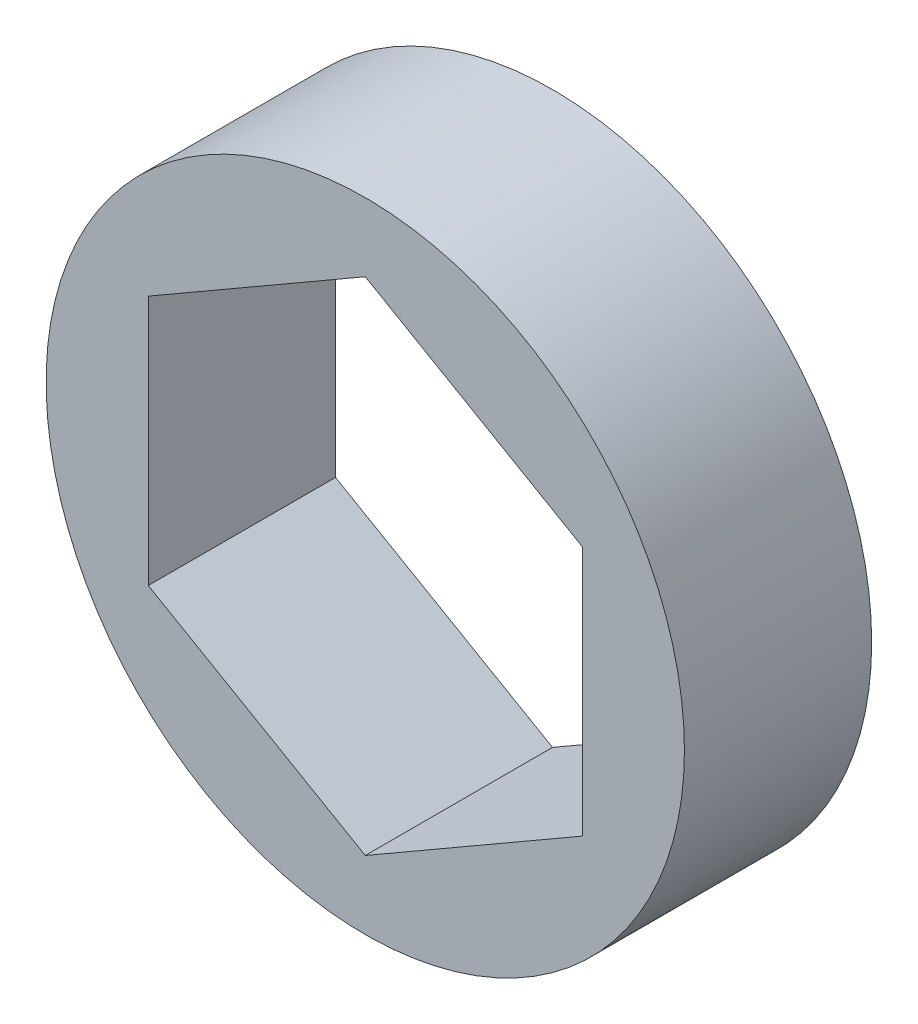
SolidWorks part; units mm, degrees
material "PET"
ref_plane "Front" through (0, 0, 0) normal (0, 0, 1) x (1, 0, 0)
ref_plane "Top" through (0, 0, 0) normal (0, 1, 0) x (1, 0, 0)
ref_plane "Right" through (0, 0, 0) normal (1, 0, 0) x (0, 0, -1)
sketch "Sketch1" plane through (0, 0, 0) normal (0, 0, 1) x (1, 0, 0)
  line L1 (0, 7.479) -> (-6.477, 3.7395)
  line L2 (-6.477, 3.7395) -> (-6.477, -3.7395)
  line L3 (-6.477, -3.7395) -> (0, -7.479)
  line L4 (0, -7.479) -> (6.477, -3.7395)
  line L5 (6.477, -3.7395) -> (6.477, 3.7395)
  line L6 (6.477, 3.7395) -> (0, 7.479)
  circle A0 centre (0, 0) radius 9.525
  circle A1 centre (0, 0) radius 6.477 construction
  dimension "D2" = 19.05
  dimension "D1" = 12.954
extrude "Boss-Extrude1" add sketch "Sketch1" along normal blind 5.588
